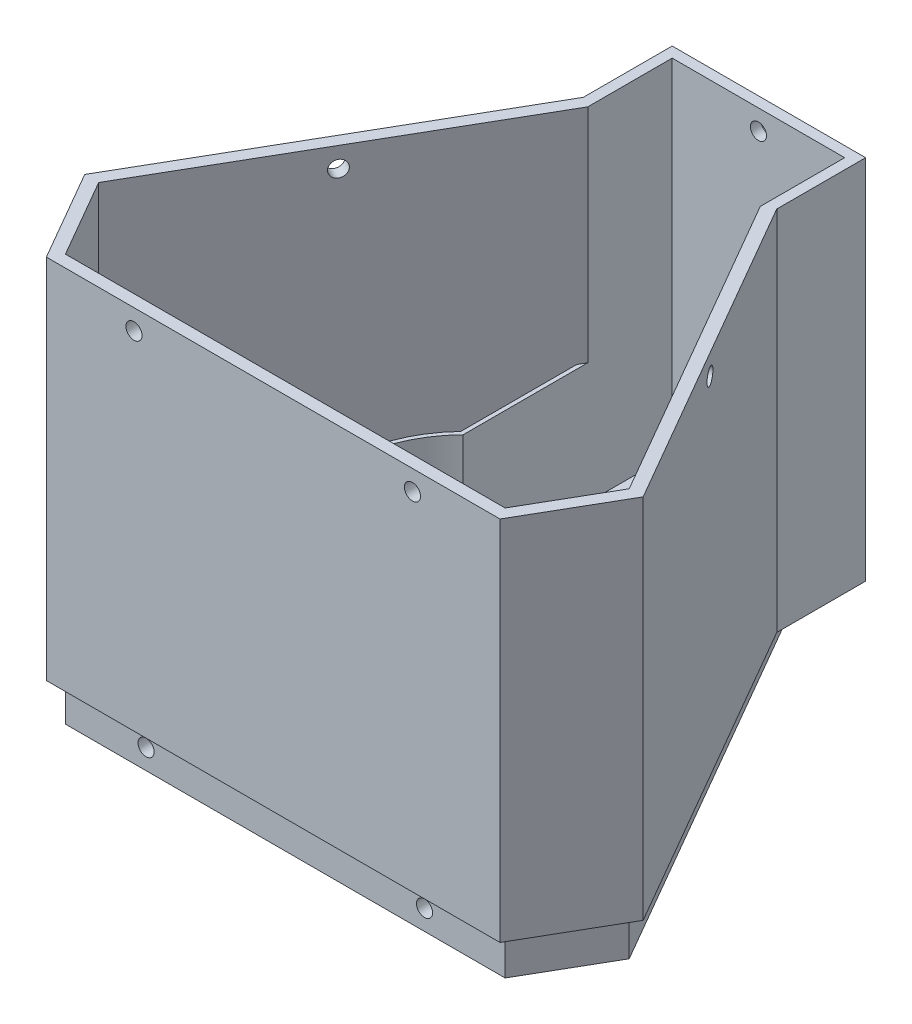
SolidWorks part; units mm, degrees
ref_plane "Front Plane" through (0, 0, 0) normal (0, 0, 1) x (1, 0, 0)
ref_plane "Top Plane" through (0, 0, 0) normal (0, 1, 0) x (1, 0, 0)
ref_plane "Right Plane" through (0, 0, 0) normal (1, 0, 0) x (0, 0, -1)
sketch "Sketch1" plane through (0, 0, 0) normal (0, 1, 0) x (1, 0, 0)
  line L0 (0, 44.1373) -> (0, -47.5886) construction
  line L1 (0, 0) -> (44.414, 25.6424) construction
  line L2 (-13, 72.4944) -> (13, 72.4944)
  line L3 (13, 72.4944) -> (21.4, 57.9452)
  line L4 (-11.2679, 69.4944) -> (11.2679, 69.4944)
  line L5 (11.2679, 69.4944) -> (38.5429, 22.2528)
  line L6 (-9.5359, 66.4944) -> (9.5359, 66.4944)
  line L7 (9.5359, 66.4944) -> (35.9449, 20.7528)
  line L8 (-24, 75.4944) -> (24, 75.4944)
  line L9 (24, 75.4944) -> (24, 53.4419)
  line L10 (-21.4, 72.8944) -> (21.4, 72.8944)
  line L11 (21.4, 72.8944) -> (21.4, 51.9452)
  line L12 (-21.4, 72.8944) -> (-21.4, 51.9452)
  line L13 (-24, 75.4944) -> (-24, 53.4419)
  line L14 (-9.5359, 66.4944) -> (-35.9449, 20.7528)
  line L15 (-11.2679, 69.4944) -> (-38.5429, 22.2528)
  line L16 (-13, 72.4944) -> (-21.4, 57.9452)
  line L17 (69.282, -24.9889) -> (41.141, 23.7528)
  line L18 (65.8179, -24.9889) -> (38.5429, 22.2528)
  line L19 (62.3538, -24.9889) -> (35.9449, 20.7528)
  line L20 (69.282, -24.9889) -> (56.282, -47.5056)
  line L21 (65.8179, -24.9889) -> (54.55, -44.5056)
  line L22 (62.3538, -24.9889) -> (52.8179, -41.5056)
  line L23 (56.282, -47.5056) -> (0, -47.5056)
  line L24 (54.55, -44.5056) -> (0, -44.5056)
  line L25 (52.8179, -41.5056) -> (0, -41.5056)
  line L26 (-56.282, -47.5056) -> (0, -47.5056)
  line L27 (-54.55, -44.5056) -> (0, -44.5056)
  line L28 (-52.8179, -41.5056) -> (0, -41.5056)
  line L29 (-56.282, -47.5056) -> (-69.282, -24.9889)
  line L30 (-54.55, -44.5056) -> (-65.8179, -24.9889)
  line L31 (-52.8179, -41.5056) -> (-62.3538, -24.9889)
  line L32 (-69.282, -24.9889) -> (-41.141, 23.7528)
  line L33 (-65.8179, -24.9889) -> (-38.5429, 22.2528)
  line L34 (-62.3538, -24.9889) -> (-35.9449, 20.7528)
  line L35 (24, 53.4419) -> (41.141, 23.7528)
  line L36 (-24, 53.4419) -> (-41.141, 23.7528)
  circle A0 centre (0, 0) radius 6
  circle A1 centre (0, 0) radius 8.6
  circle A2 centre (0, 0) radius 9.6
  point P22 (0, 72.8944)
  point P24 (0, 75.4944)
  point P26 (0, 66.4944)
  point P28 (0, 69.4944)
  point P30 (0, 72.4944)
  point P57 (0, 0)
  dimension "D12" = 12
  dimension "D13" = 17.2
  dimension "D14" = 19.2
  dimension "D1" = 3
  dimension "D2" = 42.8
  dimension "D3" = 3
  dimension "D4" = 3
  dimension "D5" = 3
  dimension "D6" = 3
  dimension "D7" = 2.6
  dimension "D8" = 26
  dimension "D10" = 120
  dimension "D11" = 2.6
  dimension "D9" = 3
extrude "Boss-Extrude1" add sketch "Sketch1" along normal blind 10 contours A1 A0 | A2 A1 | L34 L31 L28 L25 L22 L19 L7 L6 L14 A2 | L33 L30 L27 L24 L21 L18 L5 L4 L15 L31 L34 L14 L6 L7 L19 L22 L25 L28 region at (-14.8259, 0, -59.8491) region at (0, 0, -64.8447) region at (-8.3568, 0, 0) region at (-9.3285, 0, 0)
extrude "Boss-Extrude2" add sketch "Sketch1<3>" along normal blind 6 from surface contours L13 L36 L32 L29 L26 L23 L20 L17 L35 L9 L8 L30 L33 L15 L12 L10 L11 L5 L18 L21 L24 L27 | L34 L31 L28 L25 L22 L19 L7 L6 L14 | L16 L2 L3 L11 L10 L12 | L2 L16 L12 L15 L4 L5 L11 L3 | L33 L30 L27 L24 L21 L18 L5 L4 L15 L31 L34 L14 L6 L7 L19 L22 L25 L28 | A2 A1 | A1 A0 region at (-17.5926, 0, -65.4465) region at (0, 0, -72.0197) region at (-14.8259, 0, -59.8491) region at (0, 0, -64.8447) region at (0, 0, -73.6416) region at (-8.3568, 0, 0) region at (-9.3285, 0, 0) starting at face at (0, 10, 6)
sketch "Sketch1<3>" plane through (0, 0, 0) normal (0, 1, 0) x (1, 0, 0) same geometry as "Sketch1"
extrude "Boss-Extrude3" add sketch "Sketch1<4>" along normal blind 85 from surface contours L13 L36 L32 L29 L26 L23 L20 L17 L35 L9 L8 L30 L33 L15 L12 L10 L11 L5 L18 L21 L24 L27 region at (0, 0, -73.6416) starting at face at (0, 16, -14.1105)
sketch "Sketch1<4>" plane through (0, 0, 0) normal (0, 1, 0) x (1, 0, 0) same geometry as "Sketch1"
sketch "Sketch3" plane through (38.5429, 0, -22.2528) normal (0.866, 0, -0.5) x (-0.5, 0, -0.866)
  line L0 (-54.55, 5) -> (54.55, 5) construction
  line L1 (-54.55, 10) -> (-54.55, 0) construction
  line L2 (54.55, 10) -> (54.55, 0) construction
  line L3 (0, 0) -> (0, 10) construction
  line L4 (-54.55, 10) -> (54.55, 10) construction
  line L5 (36.6862, 8.7) -> (38.8224, 5)
  line L6 (-38.8224, 5) -> (-36.6862, 1.3)
  line L7 (-36.6862, 1.3) -> (-32.4138, 1.3)
  line L8 (-32.4138, 1.3) -> (-30.2776, 5)
  line L9 (-30.2776, 5) -> (-32.4138, 8.7)
  line L10 (-32.4138, 8.7) -> (-36.6862, 8.7)
  line L11 (-36.6862, 8.7) -> (-38.8224, 5)
  line L12 (32.4138, 8.7) -> (36.6862, 8.7)
  line L13 (30.2776, 5) -> (32.4138, 8.7)
  line L14 (32.4138, 1.3) -> (30.2776, 5)
  line L15 (36.6862, 1.3) -> (32.4138, 1.3)
  line L16 (38.8224, 5) -> (36.6862, 1.3)
  line L17 (-38.8224, 5) -> (-38.8224, 0)
  line L18 (-54.55, 0) -> (54.55, 0) construction
  line L19 (-38.8224, 0) -> (-30.2776, 0)
  line L20 (-30.2776, 0) -> (-30.2776, 5)
  line L21 (38.8224, 5) -> (38.8224, 0)
  line L22 (38.8224, 0) -> (30.2776, 0)
  line L23 (30.2776, 0) -> (30.2776, 5)
  circle A0 centre (-34.55, 5) radius 2
  circle A1 centre (-34.55, 5) radius 3.7 construction
  circle A2 centre (34.55, 5) radius 3.7 construction
  circle A3 centre (34.55, 5) radius 2
  circle A4 centre (-34.55, 5) radius 3
  circle A5 centre (34.55, 5) radius 3
  line M1 (-54.55, 0) -> (54.55, 0)
  dimension "D1" = 4
  dimension "D4" = 6
  dimension "D2" = 7.4
  dimension "D3" = 20
extrude "Cut-Extrude1" cut sketch "Sketch3" against normal blind 3 contours A0 | A3 region at (55.8179, 5, 7.6684) region at (21.2679, 5, -52.1739)
extrude "Cut-Extrude7" cut sketch "Sketch3<8>" against normal blind 6 from offset 3 contours L10 L11 L6 L7 L8 L9 A0 | L20 L8 L7 L6 L17 M1 | L16 L5 L12 L13 L14 L15 A3 | L23 L21 L16 L15 L14 M1 | A3 | A4 A0 | A0 | A5 A3 region at (55.8179, 0.099, 7.6684) region at (19.7147, 6.7935, -54.8642) region at (19.1813, 2.5, -55.7882) region at (54.2647, 3.2065, 4.9782) region at (55.8179, 5, 7.6684) region at (21.2679, 5, -52.1739) region at (57.2755, 5, 10.193) region at (22.7255, 5, -49.6493) offset against normal yes
sketch "Sketch3<8>" plane through (38.5429, 0, -22.2528) normal (0.866, 0, -0.5) x (-0.5, 0, -0.866) same geometry as "Sketch3"
extrude "Cut-Extrude8" cut sketch "Sketch3<11>" against normal blind 16 from offset 3 contours A4 A0 | A5 A3 | A0 | A3 region at (55.8179, 5, 7.6684) region at (21.2679, 5, -52.1739) region at (57.2755, 5, 10.193) region at (22.7255, 5, -49.6493) offset against normal yes
sketch "Sketch3<11>" plane through (38.5429, 0, -22.2528) normal (0.866, 0, -0.5) x (-0.5, 0, -0.866) same geometry as "Sketch3"
ref_axis "Axis1" through (0, -5.05, 0) along (0, 1, 0)
pattern_circular "CirPattern1" count 3 over 360 about axis through (0, -5.05, 0) along (0, 1, 0) of "Cut-Extrude1", "Cut-Extrude7", "Cut-Extrude8"
sketch "Sketch4" plane through (0, 0, -72.8944) normal (0, 0, 1) x (1, 0, 0)
  line L0 (0, 101) -> (0, 16) construction
  line L1 (21.4, 101) -> (-21.4, 101) construction
  line L2 (21.4, 16) -> (-21.4, 16) construction
  circle A0 centre (0, 30) radius 2
  circle A1 centre (0, 96) radius 2
  dimension "D2" = 4
  dimension "D4" = 4
  dimension "D1" = 14
  dimension "D3" = 5
extrude "Cut-Extrude9" cut sketch "Sketch4" against normal blind 16
sketch "Sketch5" plane through (0, 16, 0) normal (0, 1, 0) x (1, 0, 0)
  line L0 (21.4, 51.9452) -> (21.4, 21.0247)
  line L1 (-21.4, 21.0247) -> (-21.4, 51.9452)
  line L2 (22.4, 50.2132) -> (22.4, 21.4299)
  line L3 (65.8179, -24.9889) -> (21.4, 51.9452) construction
  line L4 (-22.4, 21.4299) -> (-22.4, 50.2132)
  line L5 (-21.4, 51.9452) -> (-65.8179, -24.9889) construction
  line L6 (-22.4, 50.2132) -> (-21.4, 51.9452)
  line L7 (22.4, 50.2132) -> (21.4, 51.9452)
  arc A0 (21.4, 21.0247) -> (-21.4, 21.0247) centre (0, 0) cw
  arc A1 (22.4, 21.4299) -> (-22.4, 21.4299) centre (0, 0) cw
  dimension "D2" = 1
  dimension "D3" = 60
  dimension "D4" = 62
  dimension "D1" = 1
extrude "Boss-Extrude4" add sketch "Sketch5" along normal blind 30
sketch "Sketch6" plane through (41.141, 0, -23.7528) normal (0.866, 0, -0.5) x (-0.5, 0, -0.866)
  line L0 (-11, 101) -> (-11, 10) construction
  line L1 (34.282, 101) -> (-56.282, 101) construction
  line L2 (34.282, 10) -> (-56.282, 10) construction
  circle A0 centre (-11, 96) radius 2
  dimension "D1" = 4
  dimension "D2" = 5
extrude "Cut-Extrude10" cut sketch "Sketch6" against normal blind 30
sketch "Sketch8" plane through (0, 0, 44.5056) normal (0, 0, -1) x (-1, 0, 0)
  line L0 (54.55, 101) -> (-54.55, 101) construction
  line L1 (-54.55, 101) -> (-54.55, 16) construction
  circle A0 centre (-34.55, 96) radius 2
  dimension "D3" = 4
  dimension "D1" = 5
  dimension "D2" = 20
extrude "Cut-Extrude11" cut sketch "Sketch8" against normal blind 30
mirror "Mirror1" about plane through (0, 0, 0) normal (1, 0, 0) of "Cut-Extrude11", "Cut-Extrude10"
extrude "Cut-Extrude12" cut sketch "Sketch1<5>" against normal blind 2 from surface contours A2 A1 | A1 A0 region at (-8.3568, 0, 0) region at (-9.3285, 0, 0) starting at face at (0, 16, 6)
sketch "Sketch1<5>" plane through (0, 0, 0) normal (0, 1, 0) x (1, 0, 0) same geometry as "Sketch1"
extrude "Cut-Extrude13" cut sketch "Sketch1<6>" against normal blind 7 from surface contours A1 A0 region at (-8.3568, 0, 0) starting at face at (0, 16, 9.6)
sketch "Sketch1<6>" plane through (0, 0, 0) normal (0, 1, 0) x (1, 0, 0) same geometry as "Sketch1"
